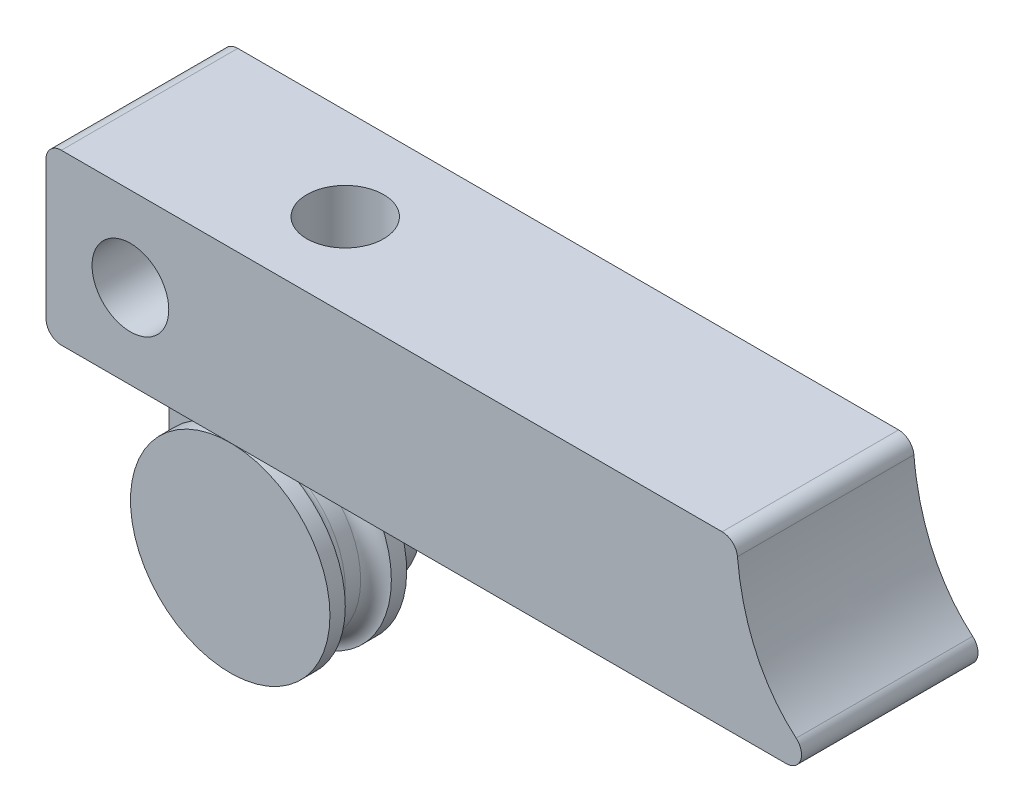
SolidWorks part; units mm, degrees
ref_plane "Front Plane" through (0, 0, 0) normal (0, 0, 1) x (1, 0, 0)
ref_plane "Top Plane" through (0, 0, 0) normal (0, 1, 0) x (1, 0, 0)
ref_plane "Right Plane" through (0, 0, 0) normal (1, 0, 0) x (0, 0, -1)
sketch "Sketch1" plane through (0, 0, 0) normal (0, 0, 1) x (1, 0, 0)
  line L0 (0, 0) -> (45, 0)
  line L1 (52, -11) -> (13, -11)
  line L2 (13, -11) -> (13, -20.5)
  line L3 (0, 0) -> (0, -20.5)
  arc A0 (0, -20.5) -> (13, -20.5) centre (6.5, -20.5) ccw
  spline S0 degree 3 poles (45, 0) (45.1676, -4.3429) (46.8949, -9.2329) (52, -11) knots 0 0 0 0 1 1 1 1
  dimension "D1" = 20.5
  dimension "D3" = 6.5
  dimension "D2" = 13
  dimension "D4" = 45
  dimension "D5" = 39
  dimension "D6" = 11
extrude "Boss-Extrude1" add sketch "Sketch1" along normal blind 3.5
sketch "Sketch2" plane through (0, 0, 3.5) normal (0, 0, 1) x (1, 0, 0)
  line L0 (0, 0) -> (0, -20.5) construction
  line L1 (13, -11) -> (52, -11) construction
  line L2 (45, 0) -> (0, 0) construction
  line L3 (0, 0) -> (0, -11)
  line L4 (13, -11) -> (52, -11)
  line L5 (45, 0) -> (0, 0)
  line L6 (13, -11) -> (0, -11)
  spline S0 degree 3 poles (1766.4377, 2445.5067) (-1437.8045, -2725.9651) (1288.5601, 2854.658) (-958.8139, -2825.3047) knots -8.023892 -8.023892 -8.023892 -8.023892 10.145467 10.145467 10.145467 10.145467 only from (52, -11) to (45, 0) construction
  spline S1 degree 3 poles (52, -11) (46.8949, -9.2329) (45.1676, -4.3429) (45, 0) knots 0 0 0 0 1 1 1 1
extrude "Boss-Extrude2" add sketch "Sketch2" along normal blind 8
fillet "Fillet1" radius 1 4 edges at (52, -11, 5.75) (45, 0, 5.75) (0, 0, 5.75) (0, -11, 7.5)
sketch "Sketch3" plane through (0, 0, 3.5) normal (0, 0, 1) x (1, 0, 0)
  line L0 (0, -20.5) -> (18.0092, -20.5) construction
  line L1 (0, -10) -> (0, -20.5) construction
  arc A0 (0, -20.5) -> (13, -20.5) centre (6.5, -20.5) ccw construction
  circle A1 centre (9.0046, -20.5) radius 1.5
  dimension "D1" = 9.0046
  dimension "D2" = 3
extrude "Cut-Extrude1" cut sketch "Sketch3" against normal blind 8
sketch "Sketch4" plane through (0, 0, 11.5) normal (0, 0, 1) x (1, 0, 0)
  line L2 (5.5, 4.085) -> (5.5, -13.7615) construction
  line L3 (0, -1) -> (0, -10) construction
  line L4 (44.062, 0) -> (1, 0) construction
  circle A0 centre (5.5, -5.5) radius 2.5
  dimension "D2" = 5.5
  dimension "D3" = 5
  dimension "D1" = 5.5
extrude "Cut-Extrude2" cut sketch "Sketch4" against normal blind 5
sketch "Sketch5" plane through (0, 0, 6.5) normal (0, 0, 1) x (1, 0, 0)
  circle A0 centre (5.5, -5.5) radius 1.5
  dimension "D1" = 3
extrude "Cut-Extrude3" cut sketch "Sketch5" against normal up to next
sketch "Sketch6" plane through (0, 0, 0) normal (0, 1, 0) x (1, 0, 0)
  line L0 (-1.9769, -6) -> (35.5854, -6) construction
  line L1 (44.062, -11.5) -> (1, -11.5) construction
  line L3 (0, -11.5) -> (0, 0) construction
  circle A0 centre (14, -6) radius 2.5
  dimension "D2" = 14
  dimension "D3" = 5
  dimension "D1" = 5.5
extrude "Cut-Extrude4" cut sketch "Sketch6" against normal blind 5
sketch "Sketch7" plane through (0, -5, 0) normal (0, 1, 0) x (1, 0, 0)
  circle A0 centre (14, -6) radius 1.5
  dimension "D1" = 3
extrude "Cut-Extrude5" cut sketch "Sketch7" against normal up to next
sketch "Sketch8" plane through (0, 0, 3.5) normal (0, 0, 1) x (1, 0, 0)
  circle A0 centre (9.0046, -20.5) radius 6.5
  dimension "D1" = 13
extrude "Boss-Extrude3" add sketch "Sketch8" along normal blind 5
sketch "Sketch9" plane through (0, 0, 8.5) normal (0, 0, 1) x (1, 0, 0)
  circle A0 centre (9.0046, -20.5) radius 5.5
  circle A1 centre (9.0046, -20.5) radius 6.5 construction
  circle A2 centre (9.0046, -20.5) radius 6.5
  dimension "D1" = 11
extrude "Cut-Extrude6" cut sketch "Sketch9" against normal blind 3 from offset 1 offset against normal yes
fillet "Fillet2" radius 1 2 edges at (14.5046, -20.5, 7.5) (14.5046, -20.5, 4.5)
